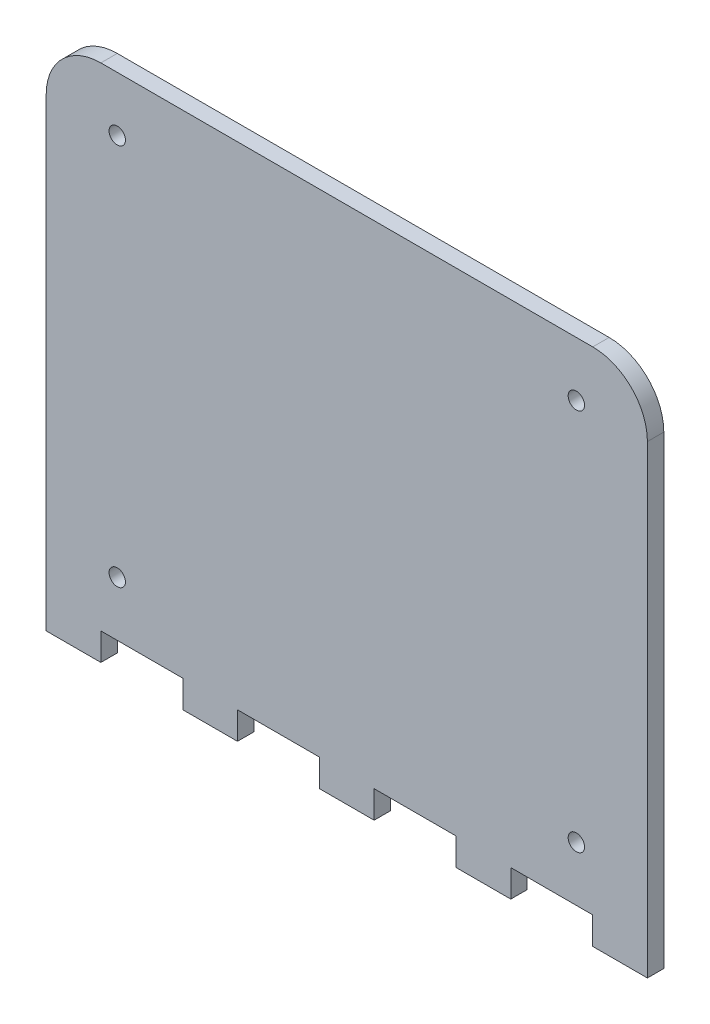
SolidWorks part; units mm, degrees
ref_plane "Спереди" through (0, 0, 0) normal (0, 0, 1) x (1, 0, 0)
ref_plane "Сверху" through (0, 0, 0) normal (0, 1, 0) x (1, 0, 0)
ref_plane "Справа" through (0, 0, 0) normal (1, 0, 0) x (0, 0, -1)
sketch "Эскиз1" plane through (0, 0, 0) normal (0, 0, 1) x (1, 0, 0)
  line L0 (-20, -45) -> (-20, -50)
  line L1 (45, -45) -> (30, -45)
  line L2 (55, -45) -> (55, 35)
  line L3 (45, 45) -> (-45, 45)
  line L4 (-55, -45) -> (-55, 35)
  line L5 (55, -45) -> (-55, 45) construction
  line L6 (55, 45) -> (-55, -45) construction
  line L12 (-55, -45) -> (-55, -50)
  line L13 (-55, -50) -> (-45, -50)
  line L14 (-45, -45) -> (-45, -50)
  line L15 (-30, -50) -> (-20, -50)
  line L16 (-30, -45) -> (-30, -50)
  line L17 (5, -45) -> (5, -50)
  line L18 (-5, -50) -> (5, -50)
  line L19 (-5, -45) -> (-5, -50)
  line L20 (30, -45) -> (30, -50)
  line L21 (20, -50) -> (30, -50)
  line L22 (20, -45) -> (20, -50)
  line L23 (55, -45) -> (55, -50)
  line L24 (45, -50) -> (55, -50)
  line L25 (45, -45) -> (45, -50)
  line L26 (-30, -45) -> (-45, -45)
  line L27 (-5, -45) -> (-20, -45)
  line L28 (20, -45) -> (5, -45)
  arc A0 (55, 35) -> (45, 45) centre (45, 35) ccw
  arc A1 (-45, 45) -> (-55, 35) centre (-45, 35) ccw
  point P0 (0, 0)
  dimension "D3" = 10
  dimension "D1" = 110
  dimension "D2" = 90
  dimension "D4" = 10
  dimension "D5" = 5
  dimension "D6" = 5
extrude "Бобышка-Вытянуть2" add sketch "Эскиз1" along normal mid plane 3
sketch "Эскиз2" plane through (0, 0, 1.5) normal (0, 0, 1) x (1, 0, 0)
  line L0 (55, -50) -> (55, 35) construction
  line L5 (45, 45) -> (-45, 45) construction
  line L6 (47, -40) -> (-47, -40) construction
  line L7 (47, -40) -> (47, 40) construction
  line L8 (47, 40) -> (-47, 40) construction
  line L9 (-47, -40) -> (-47, 40) construction
  line L10 (47, -40) -> (-47, 40) construction
  line L11 (47, 40) -> (-47, -40) construction
  point P0 (0, 0)
  dimension "D1" = 5
  dimension "D2" = 94
  dimension "D3" = 8
  dimension "D4" = 80
sketch "Эскиз3" plane through (0, 0, 1.5) normal (0, 0, 1) x (1, 0, 0)
  line L1 (47, 40) -> (-47, 40) construction
  line L3 (-47, -40) -> (-47, 40) construction
  line L4 (0, 0) -> (0, 22.2229) construction
  line L6 (0, 0) -> (-8.2285, 0) construction
  circle A0 centre (-42, 35) radius 1.5
  circle A1 centre (42, 35) radius 1.5
  circle A2 centre (42, -35) radius 1.5
  circle A3 centre (-42, -35) radius 1.5
  dimension "D1" = 5
  dimension "D2" = 5
extrude "Вырез-Вытянуть1" cut sketch "Эскиз3" against normal up to surface (3 mm away) up to face at (0, -31.6299, -1.5)
